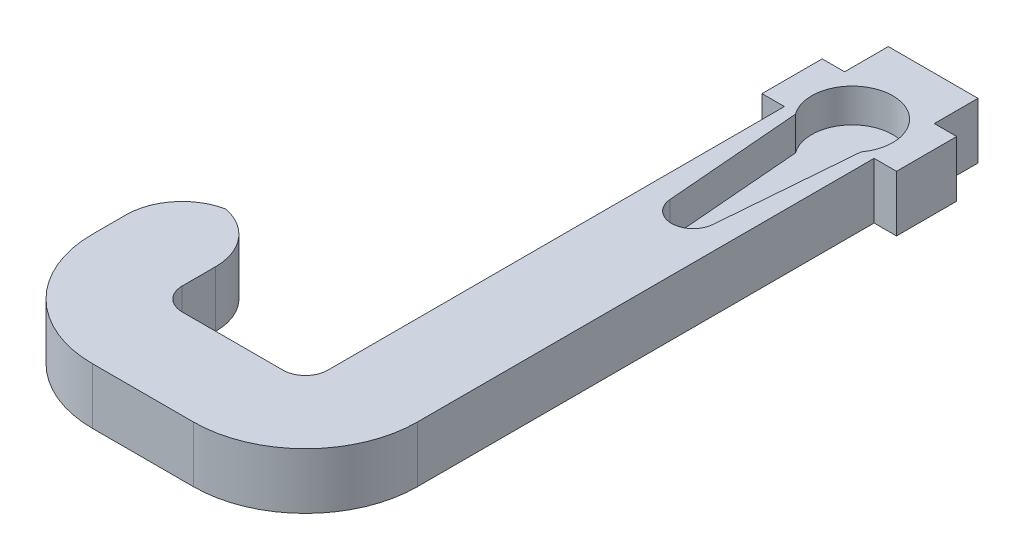
SolidWorks part; units mm, degrees
ref_plane "Front Plane" through (0, 0, 0) normal (0, 0, 1) x (1, 0, 0)
ref_plane "Top Plane" through (0, 0, 0) normal (0, 1, 0) x (1, 0, 0)
ref_plane "Right Plane" through (0, 0, 0) normal (1, 0, 0) x (0, 0, -1)
sketch "Sketch1" plane through (0, 0, 0) normal (0, 1, 0) x (1, 0, 0)
  line L0 (0, 0) -> (13, 0) construction
  line L5 (0, 4) -> (13, 4)
  line L7 (0, -4) -> (13, -4)
  line L9 (0, 4) -> (13, -4) construction
  line L10 (0, -4) -> (13, 4) construction
  line L11 (21, 52.1) -> (23, 52.1)
  line L13 (13, 4) -> (13, 46.73)
  line L14 (13, 56) -> (21, 56)
  line L15 (21, 4) -> (21, 46.73)
  line L16 (21, -4) -> (13, -4)
  line L17 (21, -4) -> (21, 4)
  line L20 (21, -4) -> (13, 4) construction
  line L21 (11, 52.1) -> (13, 52.1)
  line L26 (0, -4) -> (-8, -4)
  line L27 (0, 4) -> (0, 14)
  line L28 (0, 14) -> (-8, 14)
  line L29 (-8, -4) -> (-8, 14)
  line L30 (0, -4) -> (-8, 14) construction
  line L31 (0, 14) -> (-8, -4) construction
  line L32 (11, 52.1) -> (11, 46.73)
  line L33 (11, 46.73) -> (13, 46.73)
  line L34 (23, 52.1) -> (23, 46.73)
  line L35 (11, 52.1) -> (23, 46.73) construction
  line L36 (11, 46.73) -> (23, 52.1) construction
  line L37 (21, 46.73) -> (23, 46.73)
  line L38 (13, 52.1) -> (13, 56)
  line L39 (21, 52.1) -> (21, 56)
  point P3 (6.5, 0)
  point P5 (-4, 5)
  point P7 (17, 49.415)
  dimension "D1" = 8
  dimension "D5" = 8
  dimension "D2" = 13
  dimension "D3" = 8
  dimension "D4" = 60
  dimension "D6" = 8
  dimension "D7" = 18
  dimension "D8" = 2
  dimension "D9" = 2
  dimension "D10" = 3.9
  dimension "D11" = 9.27
extrude "Boss-Extrude1" add sketch "Sketch1" along normal blind 5
sketch "Sketch2" plane through (0, 5, 0) normal (0, 1, 0) x (1, 0, 0)
  line L0 (17, 32.664) -> (17, 52.4) construction
  line L1 (13, 46.73) -> (13, 4) construction
  line L2 (21, -4) -> (21, 46.73) construction
  line L3 (19.921, 46.6417) -> (18.9236, 34.4368)
  line L4 (14.079, 46.6417) -> (15.0764, 34.4368)
  line L5 (21, 56) -> (13, 56) construction
  arc A0 (18.9236, 34.4368) -> (15.0764, 34.4368) centre (17, 34.594) cw
  arc A1 (19.921, 46.6417) -> (14.079, 46.6417) centre (17, 48.78) ccw
  point P12 (17, 52.4)
  dimension "D1" = 19.736
  dimension "D2" = 5.842
  dimension "D3" = 1.93
  dimension "D4" = 3.62
  dimension "D5" = 3.6
extrude "Cut-Extrude3" cut sketch "Sketch2" against normal blind 3
fillet "Fillet2" radius 10 2 edges at (-8, 2.5, 4) (21, 2.5, 4)
fillet "Fillet3" radius 5 2 edges at (0, 2.5, -14) (-8, 2.5, -14)
fillet "Fillet4" radius 2 2 edges at (0, 2.5, -4) (13, 2.5, -4)
